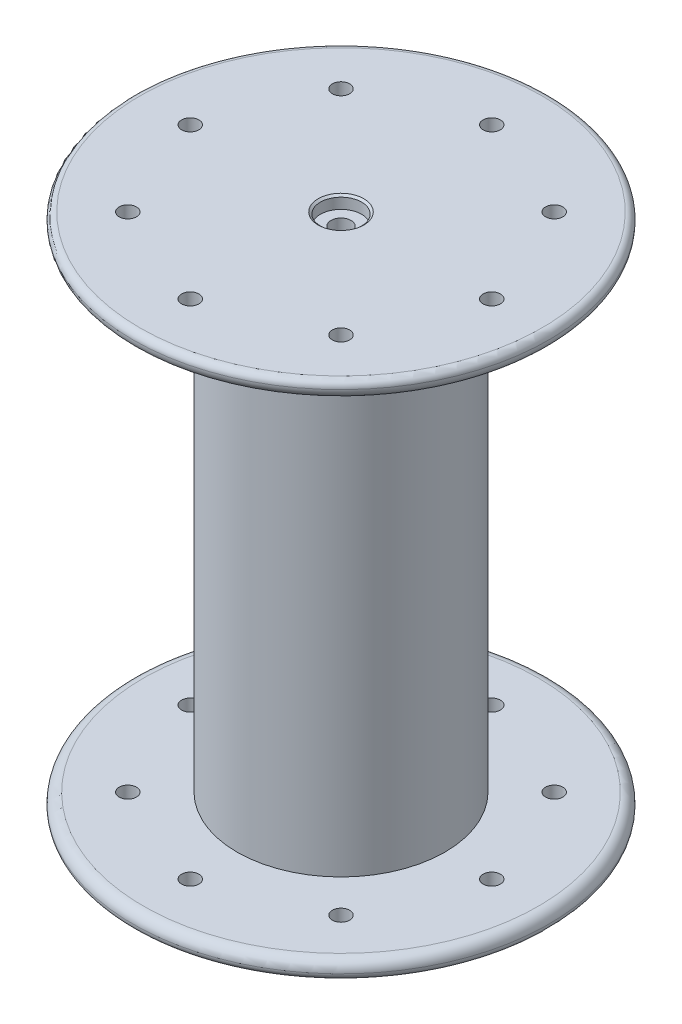
SolidWorks part; units mm, degrees
ref_plane "Front Plane" through (0, 0, 0) normal (0, 0, 1) x (1, 0, 0)
ref_plane "Top Plane" through (0, 0, 0) normal (0, 1, 0) x (1, 0, 0)
ref_plane "Right Plane" through (0, 0, 0) normal (1, 0, 0) x (0, 0, -1)
sketch "Sketch1" plane through (0, 0, 0) normal (0, 1, 0) x (1, 0, 0)
  circle A0 centre (0, 0) radius 30
  dimension "ShaftDiameter" = 60
extrude "Boss-Extrude1" add sketch "Sketch1" along normal mid plane 140
sketch "Sketch2" plane through (0, 70, 0) normal (0, 1, 0) x (1, 0, 0)
  circle A0 centre (0, 0) radius 60
  dimension "CapDiameter" = 120
extrude "Boss-Extrude2" add sketch "Sketch2" along normal blind 5
fillet "Fillet1" radius 2 1 edges at (0, 75, 60)
fillet "Fillet5" radius 3 1 edges at (0, 70, 60)
hole_wizard "CBORE for #12 Binding Head Machine Screw1" positions "Sketch4" profile "Sketch5" counterbore size "#12" standard "ANSI Inch" end condition through all
sketch "Sketch4" plane through (0, 75, 0) normal (0, 1, 0) x (1, 0, 0)
  point P0 (0, 0)
sketch "Sketch5" plane through (0, 75, 0) normal (1, 0, 0) x (0, 0, 1)
  line L0 (0, 0) -> (0, 150)
  line L1 (0, 150) -> (2.8956, 150)
  line L3 (2.8956, 150) -> (2.8956, 3.5814)
  line L4 (5.9538, 3.5814) -> (2.8956, 3.5814)
  line L5 (5.9538, 3.5814) -> (5.9538, 0.5328)
  line L6 (5.9538, 0.5328) -> (6.5888, 0)
  line L7 (6.5888, 0) -> (0, 0)
  line L8 (-5.9538, 0.5328) -> (-6.5888, 0) construction
  line L11 (0, -6.35) -> (0, 107.95) construction
  dimension "Thru Hole Dia." = 5.7912
  dimension "Thru Hole Depth" = 150
  dimension "C'Bore Dia." = 11.9075
  dimension "C'Bore Depth" = 3.5814
  dimension "Near C'Sink Dia." = 13.1775
  dimension "Near C'Sink Angle" = 100
sketch "Sketch6" plane through (0, 75, 0) normal (0, 1, 0) x (1, 0, 0)
  line L0 (0, 30) -> (0, 57) construction
  circle A1 centre (0, 0) radius 30 construction
  circle A2 centre (0, 0) radius 57 construction
  circle A3 centre (0, 43.5) radius 2.5
  dimension "D1" = 5
extrude "Cut-Extrude1" cut sketch "Sketch6" against normal through all contours A3
pattern_circular "CirPattern1" count 8 over 360 about axis through (0, 70, 0) along (0, -1, 0) of "Cut-Extrude1"
mirror "Mirror1" about plane through (0, 0, 0) normal (0, 1, 0) of "Boss-Extrude2", "Fillet1", "Fillet5", "CBORE for #12 Binding Head Machine Screw1", "Cut-Extrude1", "CirPattern1"
